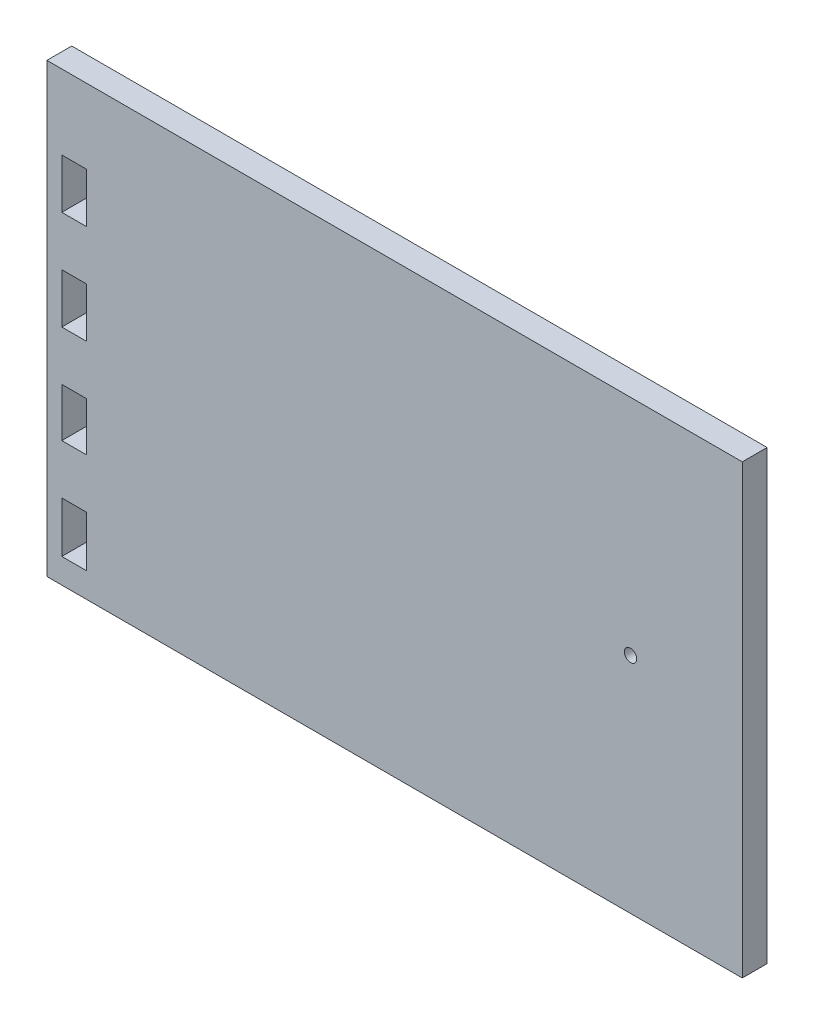
SolidWorks part; units mm, degrees
ref_plane "Front Plane" through (0, 0, 0) normal (0, 0, 1) x (1, 0, 0)
ref_plane "Top Plane" through (0, 0, 0) normal (0, 1, 0) x (1, 0, 0)
ref_plane "Right Plane" through (0, 0, 0) normal (1, 0, 0) x (0, 0, -1)
sketch "Sketch2" plane through (0, 0, 0) normal (0, 0, 1) x (1, 0, 0)
  line L1 (0, 0) -> (355.6, 0)
  line L2 (0, 0) -> (0, -228.6)
  line L3 (0, -228.6) -> (355.6, -228.6)
  line L4 (355.6, 0) -> (355.6, -228.6)
  dimension "D1" = 355.6
  dimension "D2" = 228.6
extrude "Boss-Extrude1" add sketch "Sketch2" along normal blind 12.7
sketch "Sketch3" plane through (0, 0, 12.7) normal (0, 0, 1) x (1, 0, 0)
  line L1 (355.6, -228.6) -> (355.6, 0) construction
  circle A1 centre (298.45, -114.3) radius 3.175
  dimension "D4" = 6.35
  dimension "D3" = 57.15
extrude "Cut-Extrude1" cut sketch "Sketch3" against normal blind 12.7
sketch "Sketch4" plane through (0, 0, 12.7) normal (0, 0, 1) x (1, 0, 0)
  line L1 (7.62, -38.1) -> (20.32, -38.1)
  line L2 (7.62, -38.1) -> (7.62, -63.5)
  line L3 (7.62, -63.5) -> (20.32, -63.5)
  line L4 (0, 0) -> (0, -228.6)
  line L5 (0, -228.6) -> (355.6, -228.6)
  line L6 (355.6, -228.6) -> (355.6, 0)
  line L7 (355.6, 0) -> (0, 0)
  line L8 (0, 0) -> (0, -228.6)
  line L9 (0, -228.6) -> (355.6, -228.6)
  line L10 (355.6, -228.6) -> (355.6, 0)
  line L11 (355.6, 0) -> (0, 0)
  line L12 (20.32, -38.1) -> (20.32, -63.5)
  line L13 (7.62, -88.9) -> (20.32, -88.9)
  line L14 (7.62, -88.9) -> (7.62, -114.3)
  line L15 (7.62, -114.3) -> (20.32, -114.3)
  line L16 (20.32, -88.9) -> (20.32, -114.3)
  line L17 (7.62, -139.7) -> (20.32, -139.7)
  line L18 (7.62, -139.7) -> (7.62, -164.592)
  line L19 (7.62, -164.592) -> (20.32, -164.592)
  line L20 (20.32, -139.7) -> (20.32, -164.592)
  line L21 (7.62, -189.992) -> (20.32, -189.992)
  line L22 (7.62, -189.992) -> (7.62, -215.9)
  line L23 (7.62, -215.9) -> (20.32, -215.9)
  line L24 (20.32, -189.992) -> (20.32, -215.9)
  dimension "D2" = 38.1
  dimension "D3" = 7.62
  dimension "D4" = 12.7
  dimension "D5" = 25.4
  dimension "D6" = 25.4
  dimension "D7" = 25.4
  dimension "D8" = 25.4
  dimension "D9" = 25.4
  dimension "D10" = 12.7
  dimension "D11" = 25.908
  dimension "D1" = 0
extrude "Cut-Extrude2" cut sketch "Sketch4" against normal through all contours L2 L1 L12 L3 | L14 L13 L16 L15 | L18 L17 L20 L19 | L22 L21 L24 L23
